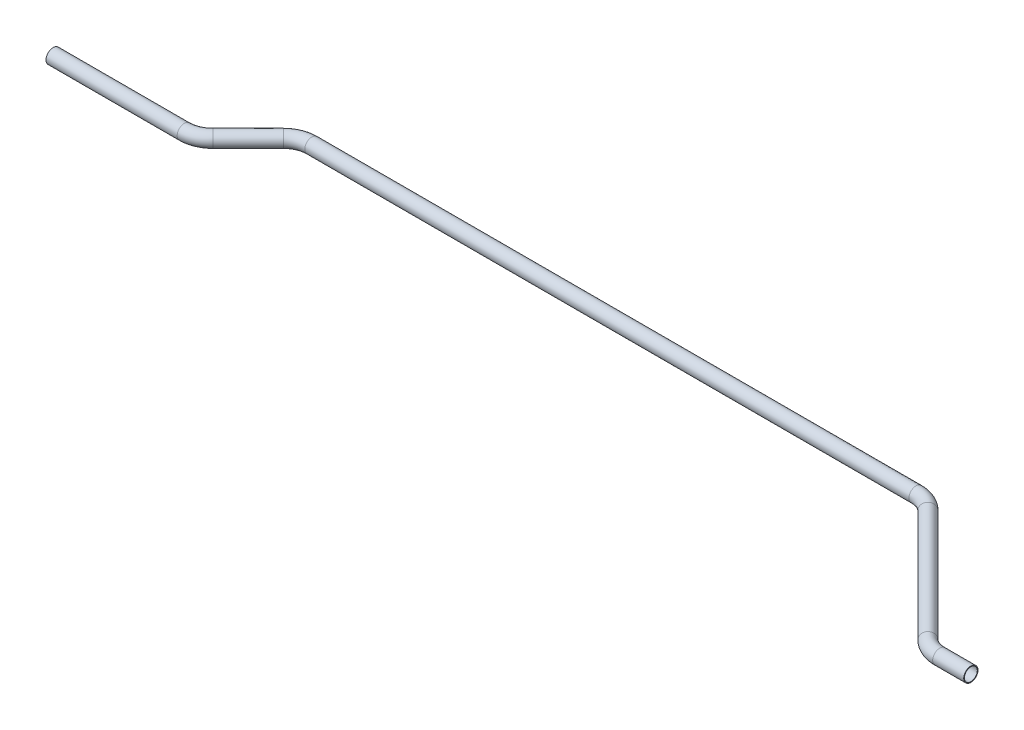
SolidWorks part; units mm, degrees
ref_plane "Front Plane" through (0, 0, 0) normal (0, 0, 1) x (1, 0, 0)
ref_plane "Top Plane" through (0, 0, 0) normal (0, 1, 0) x (1, 0, 0)
ref_plane "Right Plane" through (0, 0, 0) normal (1, 0, 0) x (0, 0, -1)
sketch "Sketch1" plane through (0, 0, 0) normal (0, 1, 0) x (1, 0, 0)
  line L0 (0, 0) -> (116.479, 0)
  line L1 (134.4395, 7.4395) -> (165.7044, 38.7044)
  line L2 (183.6649, 46.1439) -> (720.1554, 46.1439)
  line L3 (738.1159, 38.7044) -> (837.5369, -60.7167)
  line L4 (855.4974, -68.1561) -> (883.0764, -68.1561)
  arc A0 (837.5369, -60.7167) -> (855.4974, -68.1561) centre (855.4974, -42.7561) ccw
  arc A1 (720.1554, 46.1439) -> (738.1159, 38.7044) centre (720.1554, 20.7439) cw
  arc A2 (165.7044, 38.7044) -> (183.6649, 46.1439) centre (183.6649, 20.7439) cw
  arc A3 (116.479, 0) -> (134.4395, 7.4395) centre (116.479, 25.4) ccw
  point P9 (844.9764, -68.1561)
  point P12 (730.6764, 46.1439)
  point P15 (173.1439, 46.1439)
  point P18 (127, 0)
  dimension "D8" = 25.4
  dimension "D1" = 127
  dimension "D2" = 135
  dimension "D3" = 38.1
  dimension "D4" = 557.5325
  dimension "D5" = 114.3
  dimension "D6" = 45
  dimension "D7" = 46.1439
ref_plane "Plane1" through (0, 0, 0) normal (1, 0, 0) x (0, 0, -1)
sketch "Sketch2" plane through (0, 0, 0) normal (1, 0, 0) x (0, 0, -1)
  circle A0 centre (0, 0) radius 6.35
  circle A1 centre (0, 0) radius 5.715
  dimension "D1" = 12.7
  dimension "D2" = 0.635
sweep "Sweep1" add profiles "Sketch2" path "Sketch1"
